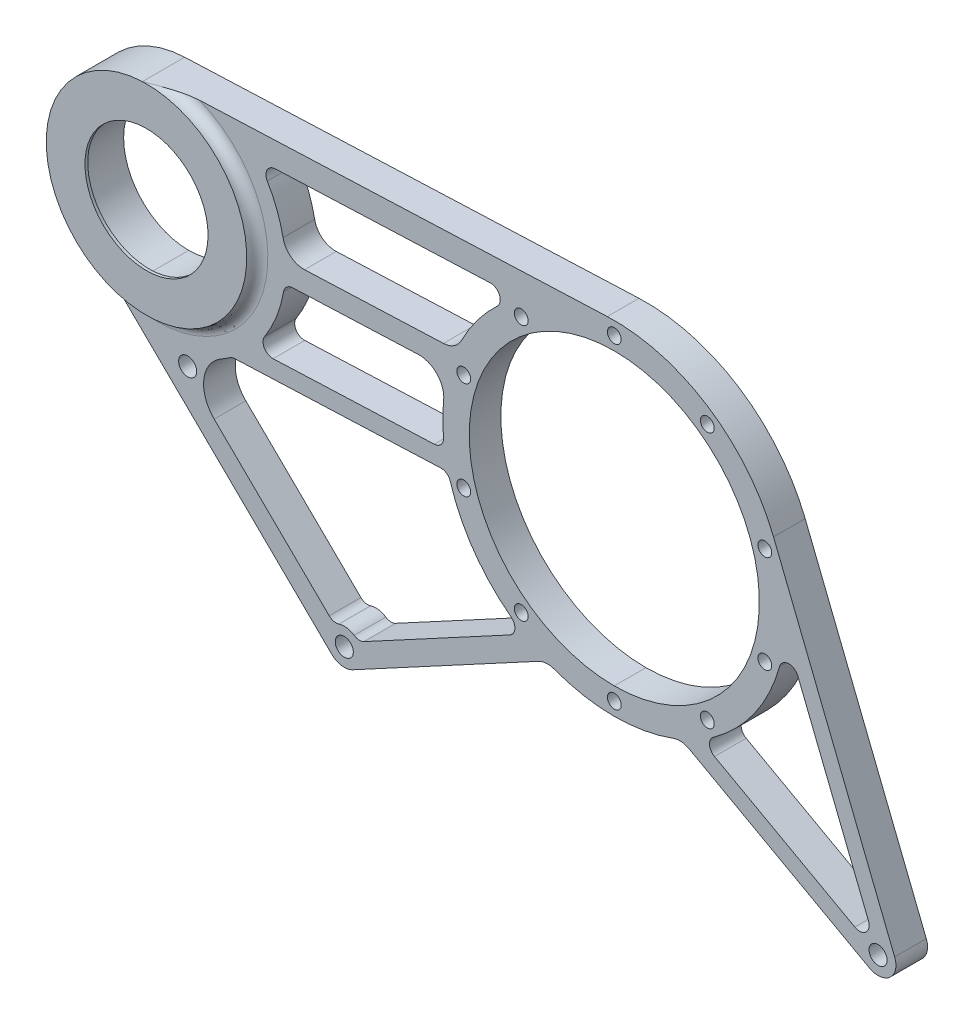
SolidWorks part; units mm, degrees
material "6061-T6 (SS)"
ref_plane "Front Plane" through (0, 0, 0) normal (0, 0, 1) x (1, 0, 0)
ref_plane "Top Plane" through (0, 0, 0) normal (0, 1, 0) x (1, 0, 0)
ref_plane "Right Plane" through (0, 0, 0) normal (1, 0, 0) x (0, 0, -1)
sketch "Sketch1" plane through (0, 0, 0) normal (0, 0, 1) x (1, 0, 0)
  line L0 (-114.3, 95.25) -> (-114.3, 107.95) construction
  line L1 (-280.8642, 163.1704) -> (-116.8043, 169.8118)
  line L2 (-304.7421, 101.1501) -> (-216.3071, 14.4521)
  line L3 (-13.0706, 21.4387) -> (-56.8054, 130.918)
  line L4 (-208.742, 13.3833) -> (-141.7118, 49.5504)
  line L5 (-22.1639, 13.4141) -> (-87.2342, 49.3665)
  circle A0 centre (-279.4, 127) radius 23.5
  circle A1 centre (-114.3, 95.25) radius 36 construction
  circle A2 centre (0, 0) radius 12.7 construction
  circle A3 centre (-228.6, 0) radius 12.7 construction
  circle A4 centre (-114.3, 107.95) radius 52.3875
  circle A5 centre (-19.05, 19.05) radius 3.2639
  circle A6 centre (-211.7995, 19.05) radius 3.2639
  circle A7 centre (-279.4, 127) radius 36.2
  arc A8 (-135.9521, 49.947) -> (-93.0137, 49.8118) centre (-114.3, 107.95) ccw
  arc A9 (-216.3071, 14.4521) -> (-208.742, 13.3833) centre (-211.7995, 19.05) ccw
  arc A10 (-22.1639, 13.4141) -> (-13.0706, 21.4387) centre (-19.05, 19.05) ccw
  arc A11 (-56.8054, 130.918) -> (-116.8043, 169.8118) centre (-114.3, 107.95) ccw
  arc A12 (-135.9521, 49.947) -> (-141.7118, 49.5504) centre (-138.3949, 43.4031) ccw
  arc A13 (-87.2342, 49.3665) -> (-93.0137, 49.8118) centre (-90.6122, 43.2526) ccw
  dimension "D5" = 72
  dimension "D6" = 47
  dimension "D7" = 25.4
  dimension "D8" = 25.4
  dimension "D11" = 104.775
  dimension "D14" = 6.5278
  dimension "D15" = 6.5278
  dimension "D16" = 25.4
  dimension "D17" = 12.7
  dimension "D18" = 123.825
  dimension "D19" = 3.175
  dimension "D20" = 6.985
  dimension "D21" = 6.985
  dimension "D1" = 114.3
  dimension "D2" = 95.25
  dimension "D3" = 279.4
  dimension "D4" = 127
  dimension "D9" = 228.6
  dimension "D10" = 12.7
  dimension "D12" = 19.05
  dimension "D13" = 19.05
extrude "Boss-Extrude1" add sketch "Sketch1" along normal blind 11.43 contours A13 L5 A10 L3 A11 L1 A7 L2 A9 L4 A12 A8 A6 A5 A4 | A7 A0 region at (-168.693, 91.0379, 0) region at (-255.035, 152.3713, 0)
sketch "Sketch2" plane through (0, 0, 11.43) normal (0, 0, 1) x (1, 0, 0)
  circle A0 centre (-279.4, 127) radius 36.2
  circle A1 centre (-279.4, 127) radius 23.5
extrude "Boss-Extrude2" add sketch "Sketch2" along normal blind 3.81
fillet "Fillet1" radius 3.81 1 edges at (-245.6173, 113.9936, 11.43)
sketch "Sketch3" plane through (0, 0, 11.43) normal (0, 0, 1) x (1, 0, 0)
  line L0 (-114.3, 107.95) -> (-114.3, 165.1) construction
  circle A0 centre (-114.3, 107.95) radius 57.15 construction
  circle A1 centre (-114.3, 165.1) radius 2.5
  circle A2 centre (-80.7081, 154.1853) radius 2.5
  circle A3 centre (-59.9471, 125.6103) radius 2.5
  circle A4 centre (-59.9471, 90.2897) radius 2.5
  circle A5 centre (-80.7081, 61.7147) radius 2.5
  circle A6 centre (-114.3, 50.8) radius 2.5
  circle A7 centre (-147.8919, 61.7147) radius 2.5
  circle A8 centre (-168.6529, 90.2897) radius 2.5
  circle A9 centre (-168.6529, 125.6103) radius 2.5
  circle A10 centre (-147.8919, 154.1853) radius 2.5
  point P25 (-114.3, 107.95)
  dimension "D1" = 114.3
  dimension "D2" = 5
  dimension "D3" = 10
extrude "5mm Holes" cut sketch "Sketch3" against normal through all
sketch "Sketch4" plane through (0, 0, 15.24) normal (0, 0, 1) x (1, 0, 0)
  circle A0 centre (-279.4, 127) radius 22.225
  circle A1 centre (-279.4, 127) radius 23.5 construction
  circle A2 centre (-279.4, 127) radius 23.5
  dimension "D1" = 44.45
extrude "Boss-Extrude3" add sketch "Sketch4" against normal blind 1
sketch "Sketch5" plane through (0, 0, 11.43) normal (0, 0, 1) x (1, 0, 0)
  line L0 (-48.0193, 91.8071) -> (-22.5033, 27.9342)
  line L1 (-13.0706, 21.4387) -> (-56.8054, 130.918) construction
  line L2 (-78.1047, 51.5771) -> (-27.4356, 23.5816)
  line L3 (-22.1639, 13.4141) -> (-87.2342, 49.3665) construction
  line L4 (-236.7455, 156.0591) -> (-159.125, 159.2013)
  line L5 (-263.8382, 163.8596) -> (-116.8043, 169.8118) construction
  line L6 (-226.1253, 129.7972) -> (-175.9845, 131.827)
  line L7 (-230.4174, 121.9972) -> (-185.1154, 123.8311)
  line L8 (-258.7869, 66.7686) -> (-217.2302, 26.028)
  line L9 (-204.6483, 24.2506) -> (-152.0143, 52.6499)
  line L10 (-292.5742, 89.2212) -> (-216.3071, 14.4521) construction
  line L11 (-208.742, 13.3833) -> (-141.7118, 49.5504) construction
  line L12 (-237.4937, 96.2899) -> (-179.3047, 98.6455)
  line L13 (-251.3498, 89.3738) -> (-177.0086, 92.3833)
  arc A0 (-175.0426, 119.9291) -> (-175.9673, 102.4457) centre (-114.3, 107.95) ccw construction
  circle A1 centre (-211.7995, 19.05) radius 6.4389 construction
  circle A2 centre (-19.05, 19.05) radius 6.4389 construction
  arc A3 (-54.6287, 91.4427) -> (-78.4387, 57.481) centre (-114.3, 107.95) cw
  arc A4 (-48.0193, 91.8071) -> (-54.6287, 91.4427) centre (-51.2626, 90.5115) ccw
  arc A5 (-27.4356, 23.5816) -> (-22.5033, 27.9342) centre (-25.7466, 26.6385) ccw
  arc A6 (-78.1047, 51.5771) -> (-78.4387, 57.481) centre (-76.4157, 54.634) cw
  arc A7 (-233.9104, 135.9413) -> (-239.6024, 150.7781) centre (-279.4, 127) ccw construction
  arc A8 (-292.5742, 89.2212) -> (-263.8382, 163.8596) centre (-279.4, 127) ccw construction
  arc A9 (-213.7352, 25.191) -> (-208.2383, 24.4145) centre (-211.7995, 19.05) cw
  arc A10 (-156.5977, 153.1613) -> (-169.499, 135.9897) centre (-114.3, 107.95) ccw
  arc A11 (-175.9093, 114.0697) -> (-175.9673, 102.4457) centre (-114.3, 107.95) ccw
  arc A12 (-173.5263, 89.9112) -> (-151.5703, 58.5123) centre (-114.3, 107.95) ccw
  arc A13 (-239.6024, 150.7781) -> (-233.9104, 135.9413) centre (-279.4, 127) cw
  arc A14 (-233.7176, 119.1025) -> (-240.5609, 101.6865) centre (-279.4, 127) cw
  arc A15 (-240.5609, 101.6865) -> (-233.7176, 119.1025) centre (-279.4, 127) ccw construction
  arc A16 (-253.1835, 88.7646) -> (-256.2406, 86.8392) centre (-279.4, 127) cw
  arc A17 (-159.125, 159.2013) -> (-156.5977, 153.1613) centre (-158.9837, 155.7117) cw
  arc A20 (-236.7455, 156.0591) -> (-239.6024, 150.7781) centre (-236.6043, 152.5695) ccw
  arc A21 (-179.3047, 98.6455) -> (-175.9673, 102.4457) centre (-179.446, 102.1352) ccw
  arc A23 (-230.4174, 121.9972) -> (-233.7176, 119.1025) centre (-230.2762, 118.5075) ccw
  arc A24 (-237.4937, 96.2899) -> (-240.5609, 101.6865) centre (-237.6349, 99.7796) cw
  arc A25 (-217.2302, 26.028) -> (-213.7352, 25.191) centre (-214.7852, 28.522) ccw
  arc A26 (-204.6483, 24.2506) -> (-208.2383, 24.4145) centre (-206.3067, 27.3242) cw
  arc A27 (-152.0143, 52.6499) -> (-151.5703, 58.5123) centre (-153.6727, 55.7236) ccw
  arc A28 (-177.0086, 92.3833) -> (-173.5263, 89.9112) centre (-176.8673, 88.8936) cw
  arc A29 (-251.3498, 89.3738) -> (-253.1835, 88.7646) centre (-251.2085, 85.8842) ccw
  arc A31 (-173.5263, 89.9112) -> (-170.4887, 133.9499) centre (-114.3, 107.95) ccw construction
  arc A32 (-273.3418, 81.0375) -> (-253.1835, 88.7646) centre (-279.4, 127) ccw construction
  arc A33 (-258.7869, 66.7686) -> (-256.2406, 86.8392) centre (-249.8962, 75.8374) cw
  arc A34 (-169.499, 135.9897) -> (-175.9845, 131.827) centre (-176.2928, 139.4407) cw
  arc A35 (-233.9104, 135.9413) -> (-226.1253, 129.7972) centre (-226.4335, 137.411) ccw
  arc A36 (-185.1154, 123.8311) -> (-175.9093, 114.0697) centre (-184.7558, 114.9484) cw
  point P17 (-52.5701, 103.1988)
  point P23 (-83.2204, 54.4036)
  point P51 (-148.3837, 159.6362)
  point P54 (-171.3442, 132.0148)
  point P60 (-243.0732, 155.8029)
  point P63 (-175.5324, 98.7982)
  point P66 (-174.02, 124.2803)
  point P75 (-215.4925, 24.3245)
  point P78 (-206.7898, 23.0951)
  point P81 (-146.981, 55.3657)
  point P84 (-174.2524, 92.4948)
  point P90 (-273.3418, 81.0375)
  dimension "D1" = 123.825
  dimension "D2" = 12.8778
  dimension "D5" = 3.4925
  dimension "D6" = 6.35
  dimension "D14" = 3.4925
  dimension "D15" = 12.7
  dimension "D16" = 7.62
  dimension "D17" = 7.62
  dimension "D18" = 8.89
  dimension "D3" = 6.35
  dimension "D4" = 6.35
  dimension "D7" = 8.89
  dimension "D8" = 7.62
  dimension "D9" = 7.62
  dimension "D10" = 7.62
  dimension "D11" = 6.35
  dimension "D12" = 25.4
  dimension "D13" = 26.67
extrude "Cut-Extrude2" cut sketch "Sketch5" against normal through all both and the other way through all
ref_axis "Axis2" through (-279.4, 127, 14.24) along (0, 0, -1)
ref_axis "Axis1" through (-114.3, 107.95, 11.43) along (0, 0, -1)
ref_plane "Plane1" through (-114.3, 0, 0) normal (1, 0, 0) x (0, 0, -1)
ref_plane "Plane2" through (-279.4, 0, 0) normal (1, 0, 0) x (0, 0, -1)
ref_plane "Plane3" through (0, 0, 5.715) normal (0, 0, -1) x (-1, 0, 0)
ref_plane "Plane4" through (0, 0, 7.12) normal (0, 0, -1) x (-1, 0, 0)
split line "Split Line1"
split line "Split Line2"
sketch "Sketch6" plane through (0, 0, 5.715) normal (0, 0, -1) x (-1, 0, 0)
  circle A1 centre (114.3, 107.95) radius 52.3875 construction
sketch "Sketch7" plane through (0, 0, 7.12) normal (0, 0, -1) x (-1, 0, 0)
  circle A0 centre (279.4, 127) radius 23.5
sketch "Sketch8" plane through (0, 0, 11.43) normal (0, 0, 1) x (1, 0, 0)
  circle A0 centre (-268.3542, 78.4783) radius 3.2639
extrude "Cut-Extrude3" cut sketch "Sketch8" against normal through all both and the other way through all
ref_point "Puck Center"
ref_point "Bearing Center"
sketch "Sketch9" plane through (0, 0, 0) normal (0, 0, 1) x (1, 0, 0)
